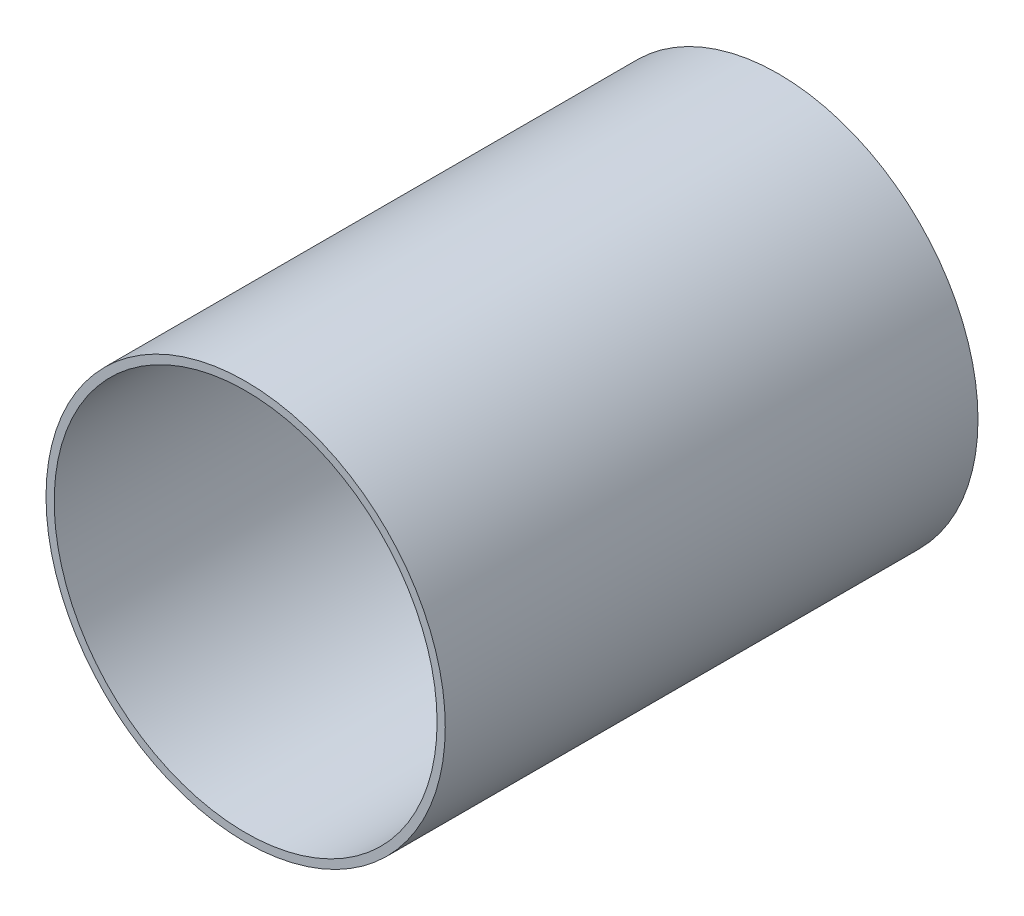
SolidWorks part; units mm, degrees
ref_plane "Front Plane" through (0, 0, 0) normal (0, 0, 1) x (1, 0, 0)
ref_plane "Top Plane" through (0, 0, 0) normal (0, 1, 0) x (1, 0, 0)
ref_plane "Right Plane" through (0, 0, 0) normal (1, 0, 0) x (0, 0, -1)
sketch "Sketch1" plane through (0, 0, 0) normal (0, 0, 1) x (1, 0, 0)
  circle A0 centre (0, 0) radius 38.0746
  circle A1 centre (0, 0) radius 36.5125
  dimension "D1" = 73.025
  dimension "D2" = 76.1492
extrude "Boss-Extrude1" add sketch "Sketch1" along normal mid plane 101.6
equation "\"AIRFRAME_OD\"= 3.142in"
equation "\"AIRFRAME_ID\"= 3.00in"
equation "\"FLAT_T\"= 0.125in"
equation "\"NOSE_EXP_L\"= 3.5in"
equation "\"NOSE_SHOULDER_L\"= 1.5in"
equation "\"MAIN_L\"= 30in"
equation "\"RECO_COUP_L\"= 6in"
equation "\"RECO_SWITCH_L\"= 1.5in"
equation "\"DROGUE_L\"= 14in"
equation "\"ATS_FORE_COUP_L\"= 4in"
equation "\"ATS_AFT_COUP_L\"= 2.5in"
equation "\"LOWER_L\"= 16in"
equation "\"FIN_N\"= 4"
equation "\"CR_AFT_X\"= 0.5in"
equation "\"CR_FORE_X\"= 6in"
equation "\"D1@Sketch1\"=\"COUPLER_ID\""
equation "\"D2@Sketch1\"=\"COUPLER_OD\""
equation "\"D1@Boss-Extrude1\"=\"ATS_FORE_COUP_L\""
equation "\"FIN_ROOT\"= 5in"
equation "\"FIN_X\"= 0.75in"
equation "\"MOTOR_OD\"= 2.25in"
equation "\"MOTOR_ID\"= 2.126in"
equation "\"COUPLER_OD\"= 2.998in"
equation "\"COUPLER_ID\"= 2.875in"
